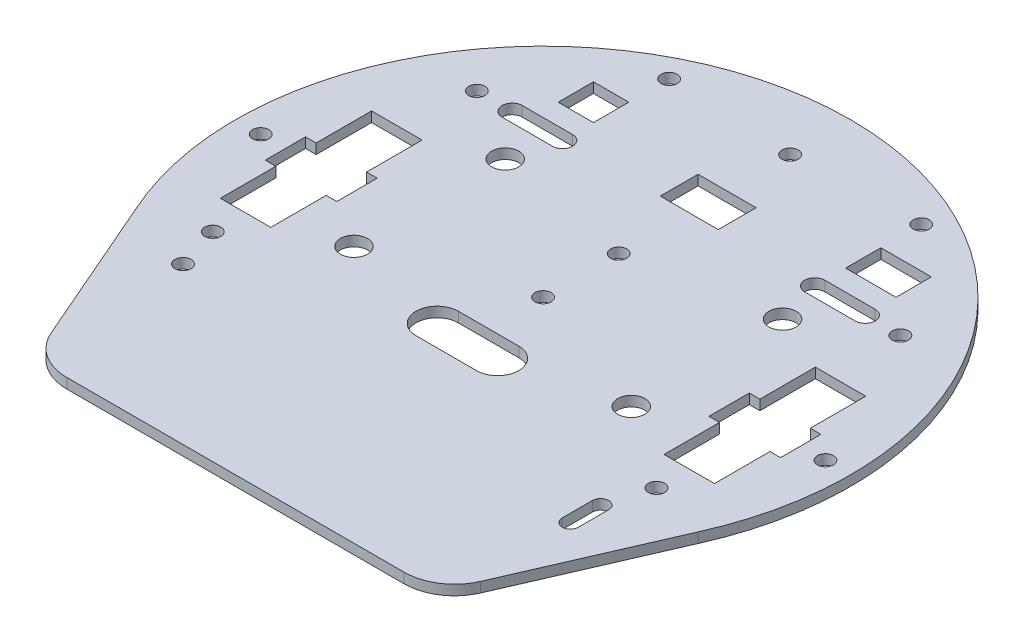
SolidWorks part; units mm, degrees
ref_plane "Front Plane" through (0, 0, 0) normal (0, 0, 1) x (1, 0, 0)
ref_plane "Top Plane" through (0, 0, 0) normal (0, 1, 0) x (1, 0, 0)
ref_plane "Right Plane" through (0, 0, 0) normal (1, 0, 0) x (0, 0, -1)
sketch "Sketch1" plane through (0, 0, 0) normal (0, 1, 0) x (1, 0, 0)
  line L0 (0, 61) -> (0, -61) construction
  line L1 (-61, 0) -> (61, 0) construction
  line L2 (49, -15) -> (39, -15)
  line L3 (-49, -15) -> (-39, -15)
  line L4 (-49, -15) -> (-49, 15)
  line L5 (-49, 15) -> (-39, 15)
  line L6 (-39, -15) -> (-39, 15)
  line L7 (-49, -15) -> (-39, 15) construction
  line L8 (-49, 15) -> (-39, -15) construction
  line L9 (49, -15) -> (49, 15)
  line L10 (49, 15) -> (39, 15)
  line L11 (49, 15) -> (39, -15) construction
  line L12 (49, -15) -> (39, 15) construction
  line L13 (39, -15) -> (39, 15)
  line L14 (-27.5, 12.8782) -> (-27.5, -19.1218) construction
  line L15 (27.5, 12.8782) -> (27.5, -19.1218) construction
  circle A0 centre (0, 0) radius 61
  circle A1 centre (-27.5, 20) radius 2.7
  circle A2 centre (-27.5, -10) radius 2.7
  circle A3 centre (27.5, -10) radius 2.7
  circle A4 centre (27.5, 20) radius 2.7
  point P7 (-44, 0)
  dimension "D1" = 122
  dimension "D5" = 5.4
  dimension "D6" = 5.4
  dimension "D7" = 20
  dimension "D8" = 10
  dimension "D2" = 30
  dimension "D3" = 10
  dimension "D4" = 39
  dimension "D9" = 55
extrude "Boss-Extrude1" add sketch "Sketch1" along normal blind 2
sketch "Sketch2" plane through (0, 2, 0) normal (0, 1, 0) x (1, 0, 0)
  line L0 (0, 0) -> (0, -41.0681) construction
  line L4 (-5.75, 29) -> (5.75, 29)
  line L5 (-5.75, 29) -> (-5.75, 36.5)
  line L6 (-5.75, 36.5) -> (5.75, 36.5)
  line L7 (5.75, 29) -> (5.75, 36.5)
  line L8 (-5.75, 29) -> (5.75, 36.5) construction
  line L9 (-5.75, 36.5) -> (5.75, 29) construction
  dimension "D1" = 29
  dimension "D4" = 7.5
  dimension "D5" = 11.5
extrude "Cut-Extrude1" cut sketch "Sketch2" against normal through all contours L4 L7 L6 L5 region at (0, 2, -32.75)
sketch "Sketch5" plane through (0, 0, 0) normal (0, -1, 0) x (1, 0, 0)
  line L0 (0, -64.6302) -> (0, 94.6302) construction
  line L1 (-45.7297, -28.872) -> (48.2791, -28.872) construction
  line L2 (-35, -28.872) -> (-25, -28.872) construction
  line L3 (-35, -26.872) -> (-25, -26.872)
  line L4 (-35, -30.872) -> (-25, -30.872)
  line L5 (35, -28.872) -> (25, -28.872) construction
  line L6 (35, -26.872) -> (25, -26.872)
  line L7 (35, -30.872) -> (25, -30.872)
  line L8 (-16.5129, 15) -> (16.6033, 15) construction
  line L9 (-6, 15) -> (6, 15) construction
  line L10 (-6, 19.2) -> (6, 19.2)
  line L11 (-6, 10.8) -> (6, 10.8)
  line L12 (-5.75, -36.5) -> (5.75, -36.5) construction
  line L13 (-32, -42) -> (-25, -42)
  line L14 (-32, -42) -> (-32, -35)
  line L15 (-32, -35) -> (-25, -35)
  line L16 (-25, -42) -> (-25, -35)
  line L17 (49, 15) -> (49, -15) construction
  line L18 (41.4, 30) -> (41.4, 36) construction
  line L19 (39.8, 30) -> (39.8, 36)
  line L20 (43, 30) -> (43, 36)
  line L21 (-49, 15) -> (-39, 15) construction
  line L22 (41.4, 30) -> (-52.5847, 30) construction
  line L23 (-32, -38.5) -> (56.2359, -38.5) construction
  line L24 (35, -35) -> (25, -35)
  line L25 (35, -35) -> (35, -42)
  line L26 (35, -42) -> (25, -42)
  line L27 (25, -35) -> (25, -42)
  line L28 (35, -35) -> (25, -42) construction
  line L29 (35, -42) -> (25, -35) construction
  arc A1 (-35, -26.872) -> (-35, -30.872) centre (-35, -28.872) ccw
  arc A2 (-25, -30.872) -> (-25, -26.872) centre (-25, -28.872) ccw
  arc A3 (35, -26.872) -> (35, -30.872) centre (35, -28.872) cw
  arc A4 (25, -30.872) -> (25, -26.872) centre (25, -28.872) cw
  arc A5 (-6, 19.2) -> (-6, 10.8) centre (-6, 15) ccw
  arc A6 (6, 10.8) -> (6, 19.2) centre (6, 15) ccw
  circle A7 centre (42, -28.872) radius 1.6
  circle A8 centre (-42, -28.872) radius 1.6
  arc A9 (39.8, 30) -> (43, 30) centre (41.4, 30) ccw
  arc A10 (43, 36) -> (39.8, 36) centre (41.4, 36) ccw
  circle A11 centre (-41.4, 30) radius 1.6
  point P9 (-30, -28.872)
  point P16 (30, -28.872)
  point P25 (0, 15)
  point P30 (0, 19.2)
  point P45 (41.4, 33)
  point P54 (30, -38.5)
  dimension "D3" = 2
  dimension "D4" = 4.2
  dimension "D11" = 3.2
  dimension "D14" = 1.6
  dimension "D18" = 3.2
  dimension "D24" = 2
  dimension "D27" = 3.2
  dimension "D2" = 10
  dimension "D5" = 6
  dimension "D6" = 1.5
  dimension "D8" = 7
  dimension "D9" = 7
  dimension "D12" = 12
  dimension "D13" = 6
  dimension "D15" = 6
  dimension "D16" = 18
  dimension "D17" = 25
  dimension "D19" = 7.6
  dimension "D20" = 25
  dimension "D21" = 25
  dimension "D22" = 28.872
  dimension "D23" = 94.0088
  dimension "D25" = 10
  dimension "D26" = 12
  dimension "D28" = 7
  dimension "D29" = 10
  dimension "D31" = 25
extrude "Cut-Extrude4" cut sketch "Sketch5" against normal through all
sketch "Sketch6" plane through (0, 2, 0) normal (0, 1, 0) x (1, 0, 0)
  line L0 (61.356, 0) -> (-61, 0) construction
  line L1 (0, -61) -> (0, 61) construction
  line L2 (51.1, 4) -> (36.9, 4)
  line L3 (51.1, 4) -> (51.1, -4)
  line L4 (51.1, -4) -> (36.9, -4)
  line L5 (36.9, 4) -> (36.9, -4)
  line L6 (51.1, 4) -> (36.9, -4) construction
  line L7 (51.1, -4) -> (36.9, 4) construction
  line L8 (-36.9, 4) -> (-36.9, -4)
  line L9 (-51.1, 4) -> (-36.9, 4)
  line L10 (-51.1, 4) -> (-51.1, -4)
  line L11 (-51.1, -4) -> (-36.9, -4)
  line L12 (44, 17.4137) -> (44, -30.0482) construction
  circle A0 centre (0, 0) radius 61 construction
  circle A1 centre (44, -21.5) radius 1.6
  circle A2 centre (-44, -21.5) radius 1.6
  circle A3 centre (-44, 21.5) radius 1.6
  circle A4 centre (44, 21.5) radius 1.6
  circle A5 centre (0, 15) radius 1.6
  circle A6 centre (0, 0) radius 1.6
  circle A7 centre (-56, 0) radius 1.6
  circle A8 centre (56, 0) radius 1.6
  circle A9 centre (-25, 50) radius 1.6
  circle A10 centre (25, 50) radius 1.6
  circle A11 centre (0, 49) radius 1.6
  point P5 (44, 0)
  line M25 (-39, 15) -> (-39, -15)
  line M27 (-49, -15) -> (-49, 15)
  line M29 (49, 15) -> (49, -15)
  line M31 (39, -15) -> (39, 15)
  dimension "D4" = 3.2
  dimension "D5" = 21.5
  dimension "D6" = 3.2
  dimension "D7" = 3.2
  dimension "D8" = 15
  dimension "D9" = 3.2
  dimension "D10" = 5
  dimension "D11" = 3.2
  dimension "D12" = 11
  dimension "D13" = 25
  dimension "D14" = 3.2
  dimension "D1" = 44
  dimension "D2" = 14.2
  dimension "D3" = 8
extrude "Cut-Extrude5" cut sketch "Sketch6" against normal through all contours L11 L9 M27 M25 | A7 | L4 L2 M29 M31 | A8 | A2 | A5 | A10 | A11 | A9 | A6 | L11 L8 L9 M25 | L10 L11 L9 M27 | L4 L3 L2 M29 | L2 L5 L4 M31 | A1 region at (50.05, 2, 0) region at (44, 2, 0) region at (37.95, 2, 0) region at (-37.95, 2, 0) region at (-44, 2, 0) region at (-50.05, 2, 0) region at (-44, 2, 21.5) region at (0, 2, -15) region at (0, 2, 0) region at (-56, 2, 0) region at (56, 2, 0) region at (-25, 2, -50) region at (25, 2, -50) region at (0, 2, -49)
sketch "Sketch7" plane through (0, 2, 0) normal (0, 1, 0) x (1, 0, 0)
  line L0 (0, 0) -> (0, -65.9406) construction
  line L1 (-40, -61) -> (40, -61)
  line L2 (56.2163, -23.6797) -> (40, -61)
  line L3 (-56.2163, -23.6797) -> (-40, -61)
  circle A0 centre (0, 0) radius 61 construction
  circle A1 centre (0, 0) radius 61
  point P10 (0, -61)
  dimension "D1" = 40
extrude "Boss-Extrude2" add sketch "Sketch7" against normal blind 2 contours A1 L3 L1 | A1 L1 L2 region at (-34.8916, 2, 53.2205) region at (34.8916, 2, 53.2205)
fillet "Fillet1" radius 10 2 edges at (40, 1, 61) (-40, 1, 61)
